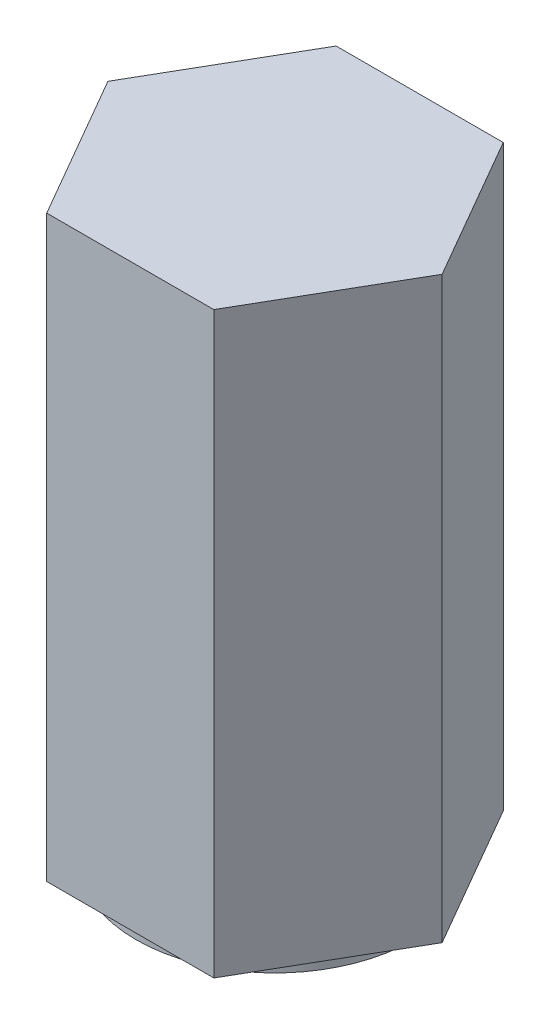
SolidWorks part; units mm, degrees
ref_plane "Alzado" through (0, 0, 0) normal (0, 0, 1) x (1, 0, 0)
ref_plane "Planta" through (0, 0, 0) normal (0, 1, 0) x (1, 0, 0)
ref_plane "Vista lateral" through (0, 0, 0) normal (1, 0, 0) x (0, 0, -1)
sketch "Croquis1" plane through (0, 0, 0) normal (0, 1, 0) x (1, 0, 0)
  line L1 (28.8675, 0) -> (14.4338, 25)
  line L2 (14.4338, 25) -> (-14.4338, 25)
  line L3 (-14.4338, 25) -> (-28.8675, 0)
  line L4 (-28.8675, 0) -> (-14.4338, -25)
  line L5 (-14.4338, -25) -> (14.4338, -25)
  line L6 (14.4338, -25) -> (28.8675, 0)
  circle A0 centre (0, 0) radius 25 construction
  dimension "D1" = 50
extrude "Saliente-Extruir1" add sketch "Croquis1" along normal blind 100
sketch "Croquis2" plane through (0, 0, 0) normal (0, -1, 0) x (1, 0, 0)
  circle A0 centre (0, 0) radius 24
  dimension "D1" = 48
extrude "Saliente-Extruir2" add sketch "Croquis2" along normal blind 2
sketch "Croquis3" plane through (0, -2, 0) normal (0, -1, 0) x (1, 0, 0)
  circle A0 centre (0, 0) radius 17.5
  dimension "D1" = 35
extrude "Cortar-Extruir1" cut sketch "Croquis3" against normal blind 90
fillet "Redondeo1" radius 5 1 edges at (0, 88, -17.5)
sketch "Croquis4" plane through (0, 0, 0) normal (0, 0, 1) x (1, 0, 0)
  line L0 (0, 0) -> (0, 52.76) construction
  line L1 (17.2679, -1.1433) -> (19, -2.1433)
  line L2 (19, -2.1433) -> (17.2679, -3.1433)
  line L3 (17.2679, -3.1433) -> (17.2679, -1.1433)
  dimension "D1" = 2
  dimension "D2" = 38
sketch "Croquis5" plane through (0, -2, 0) normal (0, -1, 0) x (1, 0, 0)
  circle A0 centre (0, 0) radius 19.1073
curve "Hélice/Espiral1" pitch 2.1 height 20 turns 9.5238
sweep "Cortar-Barrer2" cut profiles "Croquis4" path "Hélice/Espiral1"
